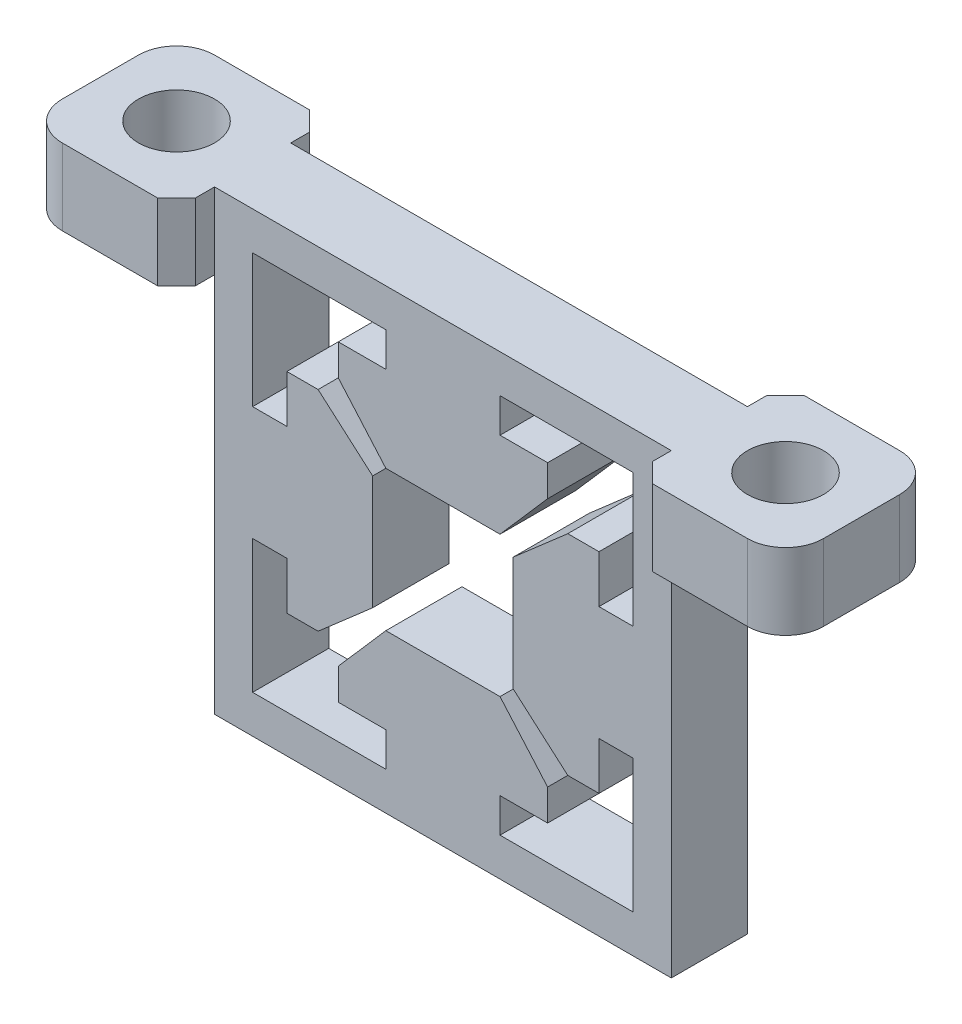
SolidWorks part; units mm, degrees
ref_plane "Спереди" through (0, 0, 0) normal (0, 0, 1) x (1, 0, 0)
ref_plane "Сверху" through (0, 0, 0) normal (0, 1, 0) x (1, 0, 0)
ref_plane "Справа" through (0, 0, 0) normal (1, 0, 0) x (0, 0, -1)
other "Configuration Table"
sketch "Эскиз1" plane through (0, 0, 0) normal (0, 0, 1) x (1, 0, 0)
  line L0 (0, 10) -> (3, 10)
  line L1 (-10, -10) -> (10, -10)
  line L2 (-10, -10) -> (-10, 10)
  line L3 (-10, 10) -> (10, 10)
  line L4 (10, -10) -> (10, 10)
  line L5 (0, 10) -> (-3, 10)
  line L6 (-3, 10) -> (-3, 8.2)
  line L7 (3, 10) -> (3, 8.2)
  line L8 (0, 10) -> (-5.5, 10)
  line L9 (0, 10) -> (5.5, 10)
  line L10 (-3, 8.2) -> (-5.5, 8.2)
  line L11 (3, 8.2) -> (5.5, 8.2)
  line L12 (-5.5, 8.2) -> (-5.5, 6.56)
  line L13 (5.5, 8.2) -> (5.5, 6.56)
  line L14 (-3, 3.694) -> (3, 3.694)
  line L15 (5.5, 8.2) -> (5.5, 6.56)
  line L16 (-5.5, 8.2) -> (-5.5, 6.56)
  line L17 (-3, 3.694) -> (-5.5, 6.56)
  line L18 (3, 3.694) -> (5.5, 6.56)
  line L19 (-10, 0) -> (10, 0) construction
  line L20 (-10, -3) -> (-8.2, -3)
  line L21 (-10, 3) -> (-8.2, 3)
  line L22 (-8.2, -3) -> (-8.2, -5.5)
  line L23 (-8.2, 3) -> (-8.2, 5.5)
  line L24 (-8.2, -5.5) -> (-6.56, -5.5)
  line L25 (-8.2, 5.5) -> (-6.56, 5.5)
  line L26 (-3.694, -3) -> (-3.694, 3)
  line L27 (-3.694, -3) -> (-6.56, -5.5)
  line L28 (-3.694, 3) -> (-6.56, 5.5)
  line L29 (0, 10) -> (0, -10) construction
  line L30 (10, 3) -> (8.2, 3)
  line L31 (10, -3) -> (8.2, -3)
  line L32 (8.2, 3) -> (8.2, 5.5)
  line L33 (8.2, -3) -> (8.2, -5.5)
  line L34 (8.2, 5.5) -> (6.56, 5.5)
  line L35 (8.2, -5.5) -> (6.56, -5.5)
  line L36 (3.694, 3) -> (3.694, -3)
  line L37 (3.694, 3) -> (6.56, 5.5)
  line L38 (3.694, -3) -> (6.56, -5.5)
  line L39 (3, -10) -> (3, -8.2)
  line L40 (-3, -10) -> (-3, -8.2)
  line L41 (3, -8.2) -> (5.5, -8.2)
  line L42 (-3, -8.2) -> (-5.5, -8.2)
  line L43 (5.5, -8.2) -> (5.5, -6.56)
  line L44 (-5.5, -8.2) -> (-5.5, -6.56)
  line L45 (3, -3.694) -> (-3, -3.694)
  line L46 (3, -3.694) -> (5.5, -6.56)
  line L47 (-3, -3.694) -> (-5.5, -6.56)
  line L48 (-12, -12) -> (12, -12)
  line L49 (12, -12) -> (12, 12)
  line L50 (-12, -12) -> (-12, 12)
  line L51 (-12, 12) -> (12, 12)
  point P34 (0, 0)
  dimension "D1" = 20
  dimension "D2" = 20
  dimension "D3" = 3
  dimension "D4" = 3
  dimension "D5" = 1.8
  dimension "D6" = 1.8
  dimension "D7" = 5.5
  dimension "D8" = 5.5
  dimension "D9" = 2.5
  dimension "D10" = 2.5
  dimension "D11" = 3
  dimension "D12" = 1.8
  dimension "D13" = 1.64
  dimension "D14" = 1.64
  dimension "D15" = 3.8032
  dimension "D16" = 3.8032
  dimension "D17" = 6
  dimension "D18" = 1.64
  dimension "D19" = 3.0806
  dimension "D20" = 4.506
  dimension "D21" = 6
  dimension "D22" = 1.8
  dimension "D23" = 1.64
  dimension "D24" = 3.8032
  dimension "D25" = 3
  dimension "D26" = 3
  dimension "D27" = 2
  dimension "D28" = 24
  dimension "D29" = 24
  dimension "D30" = 24
  dimension "D31" = 2
extrude "Бобышка-Вытянуть1" add sketch "Эскиз1" along normal blind 4 contours L45 L47 L44 L42 L40 L1 L39 L41 L43 L46 | L51 L50 L48 L49 L4 L1 L2 L3 L0 | L36 L38 L35 L33 L31 L4 L30 L32 L34 L37 | L26 L28 L25 L23 L21 L2 L20 L22 L24 L27 | L14 L18 L13 L11 L7 L0 L3 L6 L10 L12 L17 region at (0, 6.7618, 0) region at (6.7618, 0, 0) region at (-6.7618, 0, 0) region at (0, -6.7618, 0) region at (-11.6606, 0, 0)
sketch "Эскиз6" plane through (0, 12, 0) normal (0, 1, 0) x (1, 0, 0)
  line L1 (-12, 2) -> (-18, 2)
  line L2 (-12, 2) -> (-12, -6)
  line L3 (-12, -6) -> (-18, -6)
  line L4 (-20, 0) -> (-20, -4)
  line L9 (-12, -2) -> (-38.0803, -2) construction
  line L10 (-12, -4) -> (-12, 0) construction
  arc A0 (-18, 2) -> (-20, 0) centre (-18, 0) ccw
  arc A1 (-20, -4) -> (-18, -6) centre (-18, -4) ccw
  circle A2 centre (-16, -2) radius 2
  point P8 (-12, -2)
  point P11 (-20, 2)
  point P14 (-20, -6)
  dimension "D3" = 2
  dimension "D4" = 2
  dimension "D5" = 4
  dimension "D1" = 8
  dimension "D2" = 8
  dimension "D6" = 4
extrude "Бобышка-Вытянуть2" add sketch "Эскиз6" against normal blind 4
chamfer "Фаска1" distance 1 angle 45 2 edges at (-12, 10, -2) (-12, 10, 6)
mirror "Зеркальное отражение1" about plane through (0, 0, 0) normal (1, 0, 0) of "Фаска1", "Бобышка-Вытянуть2"
